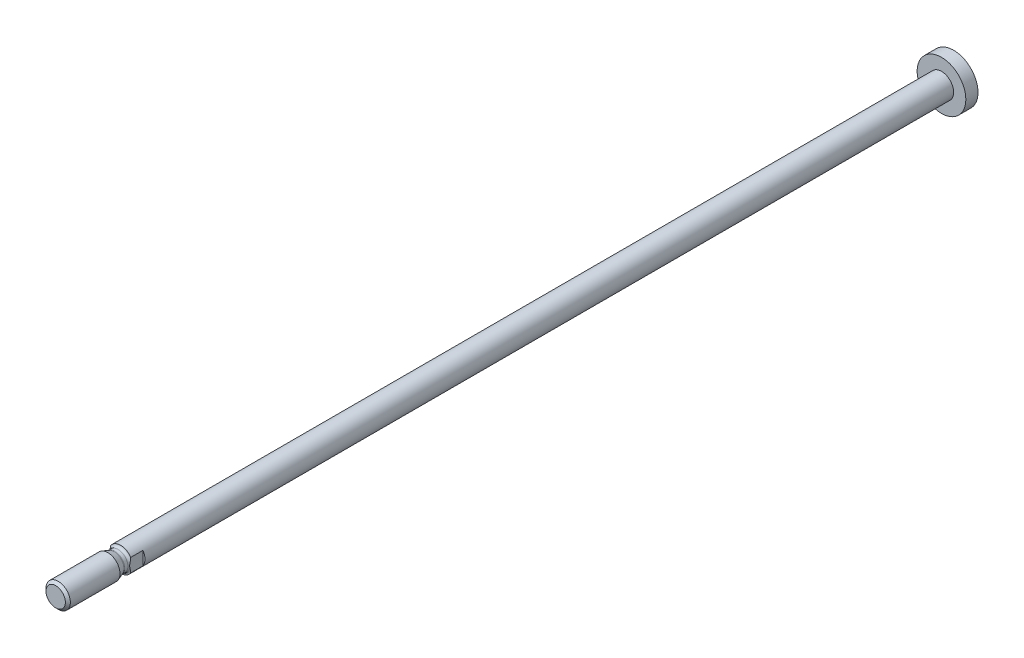
SolidWorks part; units mm, degrees
ref_plane "Ebene vorne" through (0, 0, 0) normal (0, 0, 1) x (1, 0, 0)
ref_plane "Ebene oben" through (0, 0, 0) normal (0, 1, 0) x (1, 0, 0)
ref_plane "Ebene rechts" through (0, 0, 0) normal (1, 0, 0) x (0, 0, -1)
sketch "Skizze1" plane through (0, 0, 0) normal (1, 0, 0) x (0, 0, -1)
  line L0 (-5, 0) -> (-5, 3)
  line L1 (-5, 3) -> (197.3, 3)
  line L2 (197.3, 3) -> (197.3, 6)
  line L3 (197.3, 6) -> (200.3, 6)
  line L4 (200.3, 6) -> (200.3, 0)
  line L5 (200.3, 0) -> (-5, 0)
  line L6 (200.3, 0) -> (-5, 0) construction
revolve "Rotation1" add sketch "Skizze1" angle 360 about L6 reverse direction yes
sketch "Skizze2" plane through (0, 0, 0) normal (1, 0, 0) x (0, 0, -1)
  line L0 (-21, 0) -> (-21, 2.3865)
  line L1 (-21, 2.3865) -> (-20.3865, 3)
  line L2 (-20.3865, 3) -> (-8.1485, 3)
  line L3 (-8.1485, 3) -> (-6.5994, 2.4362)
  line L4 (-6.3942, 2.4) -> (-5.6, 2.4)
  line L5 (-5, 3) -> (-4, 3)
  line L6 (-4, 3) -> (-4, 0)
  line L7 (-4, 0) -> (-21, 0)
  line L8 (-4, 0) -> (-21, 0) construction
  arc A0 (-6.5994, 2.4362) -> (-6.3942, 2.4) centre (-6.3942, 3) ccw
  arc A1 (-5.6, 2.4) -> (-5, 3) centre (-5.6, 3) ccw
revolve "Rotation2" add sketch "Skizze2" angle 360 about L8 reverse direction yes
cosmetic thread "Gewindedarstellung1" parameters "D1"=12.8515, "D2"=4.773
ref_plane "Ebene1" through (0, 0, 5) normal (0, 0, 1) x (1, 0, 0)
ref_plane "Ebene2" through (0, 0, 2) normal (0, 0, 1) x (1, 0, 0)
sketch "Skizze3" plane through (0, 0, 2) normal (0, 0, 1) x (1, 0, 0)
  line L0 (-5, 10) -> (-5, -5)
  line L1 (-5, -5) -> (-2.5, -5)
  line L2 (-2.5, -5) -> (-2.5, 5)
  line L3 (-2.5, 5) -> (2.5, 5)
  line L4 (2.5, 5) -> (2.5, -5)
  line L5 (2.5, -5) -> (5, -5)
  line L6 (5, -5) -> (5, 10)
  line L7 (5, 10) -> (-5, 10)
extrude "Schnitt-Linear austragen1" cut sketch "Skizze3" along normal blind 4
ref_plane "Ebene3" through (0, 0, -409) normal (0, 0, 1) x (1, 0, 0)
ref_plane "Ebene4" through (0, 0, 16) normal (0, 0, 1) x (1, 0, 0)
ref_plane "Ebene5" through (0, 0, 11.2) normal (0, 0, 1) x (1, 0, 0)
ref_plane "FDT_KSAUFSATZ XY" through (0, 0, 11.2) normal (0, 0, 1) x (1, 0, 0)
ref_plane "FDT_KSAUFSATZ XZ" through (0, 0, 0) normal (0, 1, 0) x (1, 0, 0)
ref_plane "FDT_KSAUFSATZ YZ" through (0, 0, 0) normal (-1, 0, 0) x (0, 0, 1)
ref_axis "FDT_KSAUFSATZ X" through (80.9, 0, 11.2) along (-1, 0, 0)
ref_axis "FDT_KSAUFSATZ Y" through (0, 50, 11.2) along (0, -1, 0)
ref_axis "FDT_KSAUFSATZ Z" through (0, 0, 80.9) along (0, 0, -1)
sketch3d "FDT_KSAUFSATZ"
  point P0 (0, 0, 11.2)
ref_plane "FDT_NUT XY" through (0, 0, 11.2) normal (0, 0, 1) x (1, 0, 0)
ref_plane "FDT_NUT XZ" through (0, 0, 0) normal (0, 1, 0) x (1, 0, 0)
ref_plane "FDT_NUT YZ" through (0, 0, 0) normal (-1, 0, 0) x (0, 0, 1)
ref_axis "FDT_NUT X" through (80.9, 0, 11.2) along (-1, 0, 0)
ref_axis "FDT_NUT Y" through (0, 50, 11.2) along (0, -1, 0)
ref_axis "FDT_NUT Z" through (0, 0, 80.9) along (0, 0, -1)
sketch3d "FDT_NUT"
  point P0 (0, 0, 11.2)
ref_plane "KS XY" through (0, 0, 0) normal (0, 0, -1) x (-1, 0, 0)
ref_plane "KS XZ" through (0, 0, 0) normal (0, 1, 0) x (1, 0, 0)
ref_plane "KS YZ" through (0, 0, 0) normal (1, 0, 0) x (0, 0, -1)
ref_axis "KS X" through (-80.9, 0, 0) along (1, 0, 0)
ref_axis "KS Y" through (0, 50, 0) along (0, -1, 0)
ref_axis "KS Z" through (0, 0, -80.9) along (0, 0, 1)
sketch3d "KS"
  point P0 (0, 0, 0)
ref_plane "NUT1 XY" through (0, 0, 16) normal (0, 0, 1) x (1, 0, 0)
ref_plane "NUT1 XZ" through (0, 0, 0) normal (0, -1, 0) x (-1, 0, 0)
ref_plane "NUT1 YZ" through (0, 0, 0) normal (1, 0, 0) x (0, 0, -1)
ref_axis "NUT1 X" through (-80.9, 0, 16) along (1, 0, 0)
ref_axis "NUT1 Y" through (0, -50, 16) along (0, 1, 0)
ref_axis "NUT1 Z" through (0, 0, 80.9) along (0, 0, -1)
sketch3d "NUT1"
  point P0 (0, 0, 16)
sketch "Sketch1" plane through (0, 0, 0) normal (1, 0, 0) x (0, 0, -1)
  line L0 (-21, 2.3865) -> (-21, -2.3865) construction
  point P0 (-51, 0)
  point P3 (0, 0)
  dimension "D1" = 30
